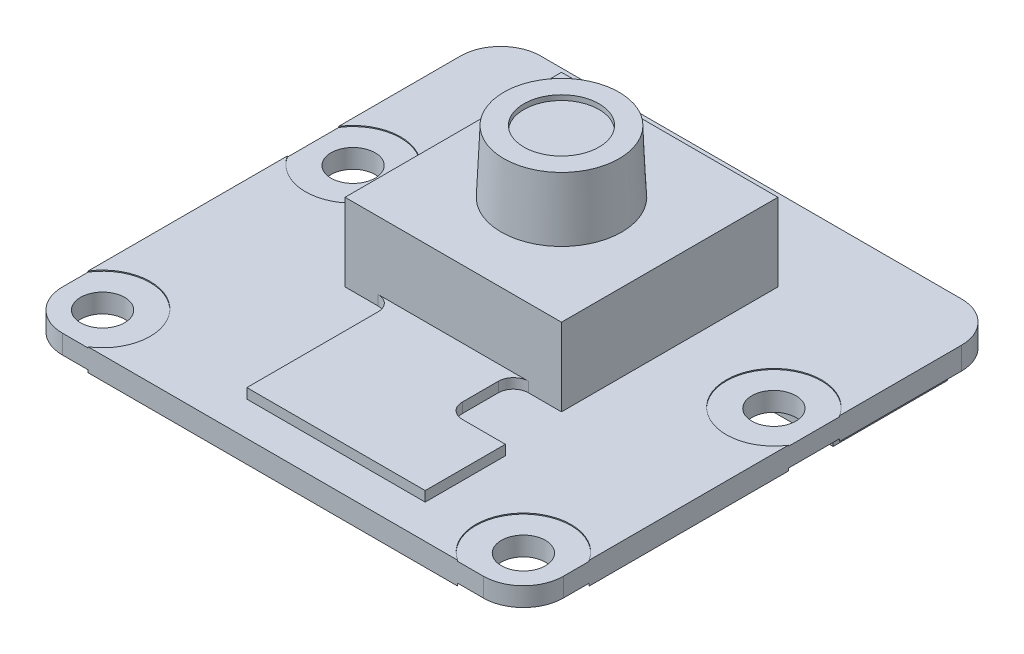
SolidWorks part; units mm, degrees
note: The reader was unsure of these and kept them because the rebuilt part matched: shared geometry of "Sketch2<3>", "Sketch3<3>".
ref_plane "Front Plane" through (0, 0, 0) normal (0, 0, 1) x (1, 0, 0)
ref_plane "Top Plane" through (0, 0, 0) normal (0, 1, 0) x (1, 0, 0)
ref_plane "Right Plane" through (0, 0, 0) normal (1, 0, 0) x (0, 0, -1)
sketch "Sketch1" plane through (0, 0, 0) normal (0, 1, 0) x (1, 0, 0)
  line L0 (0, -55) -> (0, 55) construction
  line L1 (-12.5, 9.462) -> (12.5, 9.462)
  line L2 (-12.5, 9.462) -> (-12.5, -14.4)
  line L3 (-12.5, -14.4) -> (12.5, -14.4)
  line L4 (12.5, 9.462) -> (12.5, -14.4)
  line L5 (-12.5, 9.462) -> (12.5, -14.4) construction
  line L6 (-12.5, -14.4) -> (12.5, 9.462) construction
  circle A0 centre (0, 0) radius 2.875 construction
  circle A1 centre (-10.5, -12.4) radius 1.1
  circle A2 centre (-10.5, 0.1) radius 1.1
  circle A3 centre (10.5, -12.4) radius 1.1
  circle A4 centre (10.5, 0.1) radius 1.1
  point P0 (0, -2.469)
  dimension "D4" = 5.75
  dimension "D5" = 2.2
  dimension "D8" = 2
  dimension "D1" = 23.862
  dimension "D2" = 25
  dimension "D3" = 14.4
  dimension "D6" = 2
  dimension "D7" = 2
  dimension "D9" = 14.5
extrude "Boss-Extrude1" add sketch "Sketch1" along normal blind 1.12
fillet "Fillet1" radius 2 4 edges at (12.5, 0.56, 14.4) (-12.5, 0.56, -9.462) (12.5, 0.56, -9.462) (-12.5, 0.56, 14.4)
sketch "Sketch2" plane through (0, 1.12, 0) normal (0, 1, 0) x (1, 0, 0)
  line L0 (0, -55) -> (0, 55) construction
  circle A0 centre (-10.5, -12.4) radius 2.375
  circle A1 centre (-10.5, 0.1) radius 2.375
  circle A2 centre (10.5, -12.4) radius 2.375
  circle A3 centre (10.5, 0.1) radius 2.375
  dimension "D1" = 4.75
extrude "Cut-Extrude1" cut sketch "Sketch2" against normal blind 0.05
extrude "Cut-Extrude2" cut sketch "Sketch2<3>" along normal blind 0.125 from surface at -1.12 starting at face at (0, 0, 2.469)
sketch "Sketch2<3>" plane through (0, 1.12, 0) normal (0, 1, 0) x (1, 0, 0) same geometry as "Sketch2"
sketch "Sketch3" plane through (0, 1.12, 0) normal (0, 1, 0) x (1, 0, 0)
  line L1 (-5.4, 5.4) -> (5.4, 5.4)
  line L2 (-5.4, 5.4) -> (-5.4, -5.4)
  line L3 (-5.4, -5.4) -> (5.4, -5.4)
  line L4 (5.4, 5.4) -> (5.4, -5.4)
  line L5 (-5.4, 5.4) -> (5.4, -5.4) construction
  line L6 (-5.4, -5.4) -> (5.4, 5.4) construction
  circle A0 centre (0, 0) radius 2.875
  point P0 (0, 0)
  dimension "D2" = 5.75
  dimension "D1" = 10.8
extrude "Boss-Extrude2" add sketch "Sketch3" along normal blind 3.875 separate body contours L1 L4 L3 L2
extrude "Boss-Extrude3" add sketch "Sketch3<3>" along normal blind 3.105 from surface at 3.875 contours A0 starting at face at (0, 4.995, 0)
sketch "Sketch3<3>" plane through (0, 1.12, 0) normal (0, 1, 0) x (1, 0, 0) same geometry as "Sketch3"
sketch "Sketch5" plane through (0, 8.1, 0) normal (0, 1, 0) x (1, 0, 0)
  circle A0 centre (0, 0) radius 1.875
  circle A1 centre (0, 0) radius 2.875 construction
  dimension "D1" = 1
extrude "Cut-Extrude3" cut sketch "Sketch5" against normal blind 0.25
draft "Draft1" type of draft neutral plane draft angle 2.5 faces to draft 1 face at (0, 8.1, 2.875) neutral plane through (0, 8.1, 0) neutral plane normal (0, 1, 0) parameters "D1"=2.5
sketch "Sketch6" plane through (0, 1.12, 0) normal (0, 1, 0) x (1, 0, 0)
  line L0 (5.4, 5.4) -> (5.4, -5.4) construction
  line L1 (-5.4, -5.4) -> (5.4, -5.4)
  line L2 (-5.4, -5.4) -> (-5.4, -4.4)
  line L3 (-5.4, -4.4) -> (5.4, -4.4)
  line L4 (5.4, -5.4) -> (5.4, -4.4)
  line L6 (5.9, -12.7) -> (-3, -12.7)
  line L7 (5.9, -12.7) -> (5.9, -8.7)
  line L8 (5.9, -8.7) -> (-3, -8.7)
  line L9 (-3, -12.7) -> (-3, -8.7)
  line L10 (-3, -12.7) -> (3, -12.7)
  line L11 (-3, -12.7) -> (-3, -5.4)
  line L12 (-3, -5.4) -> (3, -5.4)
  line L13 (3, -12.7) -> (3, -5.4)
  point P14 (0, -5.4)
  point P15 (0, -5.4)
  dimension "D1" = 1
  dimension "D2" = 8.9
  dimension "D3" = 3.3
  dimension "D4" = 4
  dimension "D5" = 6
extrude "Boss-Extrude4" add sketch "Sketch6" along normal blind 0.5 contours L8 L13 L1 L11 | L6 L13 L8 L9 | L13 L6 L7 L8
fillet "Fillet2" radius 0.75 3 edges at (-3, 1.37, 5.4) (3, 1.37, 5.4) (3, 1.37, 8.7)
sketch "Sketch7" plane through (0, 0, 0) normal (0, -1, 0) x (1, 0, 0)
  line L0 (10.5, -9.462) -> (-10.5, -9.462) construction
  line L1 (9.805, -9.462) -> (-9.805, -9.462)
  line L2 (9.805, -9.462) -> (9.805, -3.752)
  line L3 (9.805, -3.752) -> (-9.805, -3.752)
  line L4 (-9.805, -9.462) -> (-9.805, -3.752)
  point P6 (0, -3.752)
  dimension "D1" = 5.71
  dimension "D2" = 19.61
extrude "Boss-Extrude5" add sketch "Sketch7" along normal blind 2.75 separate body
sketch "Sketch8" plane through (0, 0, -9.462) normal (0, 0, -1) x (-1, 0, 0)
  line L12 (9.305, -0.5) -> (-9.305, -0.5)
  line L13 (-9.305, -0.5) -> (-9.305, -2.25)
  line L14 (-9.305, -2.25) -> (9.305, -2.25)
  line L15 (9.305, -2.25) -> (9.305, -0.5)
  line L16 (9.305, -0.5) -> (-9.305, -0.5)
  line L17 (-9.305, -0.5) -> (-9.305, -2.25)
  line L18 (-9.305, -2.25) -> (9.305, -2.25)
  line L19 (9.305, -2.25) -> (9.305, -0.5)
  dimension "D1" = 0.5
extrude "Cut-Extrude4" cut sketch "Sketch8" against normal offset from surface (5.21 mm away) 0.5 up to face at (0, -1.375, -3.752)
